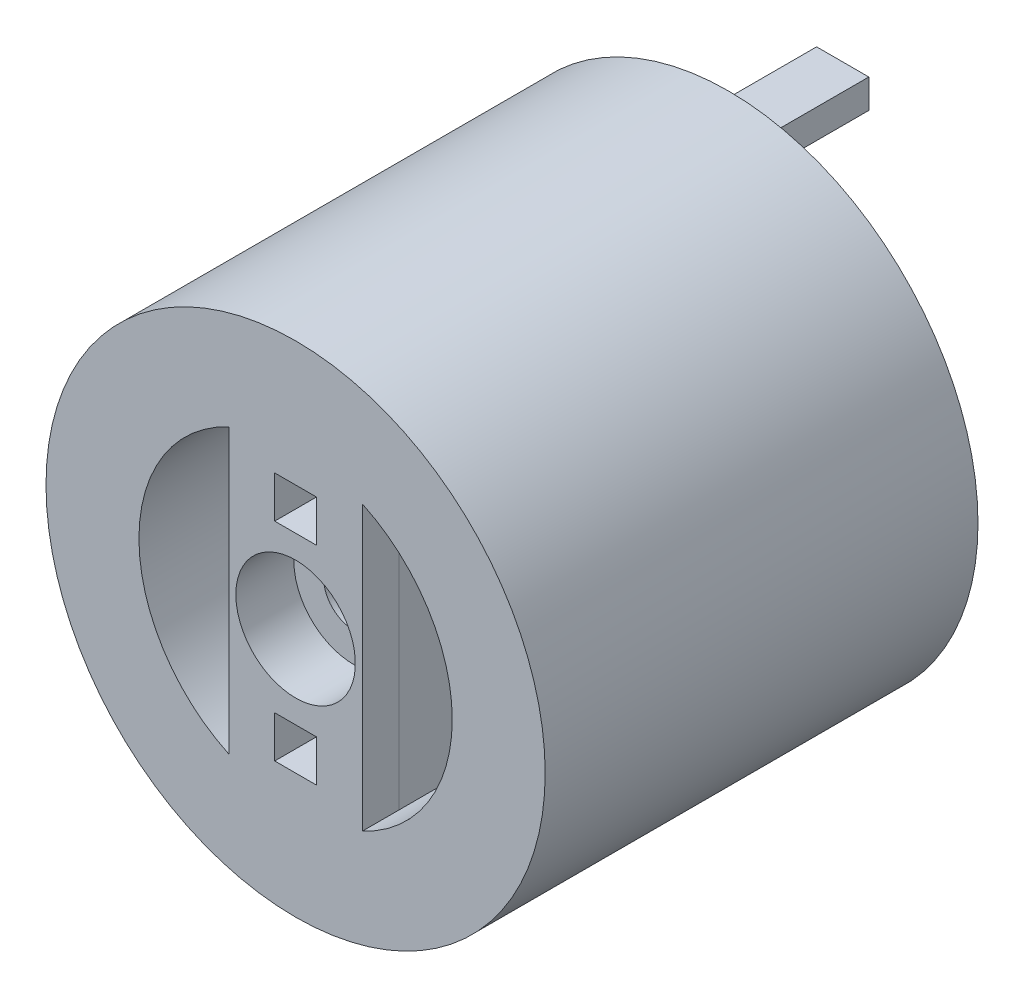
SolidWorks part; units mm, degrees
ref_plane "Front Plane" through (0, 0, 0) normal (0, 0, 1) x (1, 0, 0)
ref_plane "Top Plane" through (0, 0, 0) normal (0, 1, 0) x (1, 0, 0)
ref_plane "Right Plane" through (0, 0, 0) normal (1, 0, 0) x (0, 0, -1)
sketch "Sketch1" plane through (0, 0, 0) normal (0, 0, 1) x (1, 0, 0)
  line L0 (14.5003, 0) -> (13.5003, 0)
  line L1 (0, 16.2503) -> (0, 13.5003)
  line L3 (0, -13.5003) -> (0, -21.51)
  line L4 (13.5003, 0) -> (-13.5003, 0)
  line L8 (19.5347, 4.9654) -> (14.5348, 4.9999)
  line L9 (19.5347, 4.9654) -> (19.4657, -5.0344)
  line L10 (19.4657, -5.0344) -> (14.4659, -4.9999)
  line L11 (14.5348, 4.9999) -> (14.4659, -4.9999)
  line L24 (-2.25, 18.7503) -> (-2.25, 16.2503)
  line L25 (-2.25, 18.7503) -> (2.25, 18.7503)
  line L26 (2.25, 18.7503) -> (2.25, 16.2503)
  line L27 (-2.25, 16.2503) -> (2.25, 16.2503)
  circle A0 centre (0, 0) radius 13.5003
  circle A1 centre (0, 0) radius 21.51
  point P0 (0, 16.2503)
  point P1 (14.5003, 0)
  dimension "D3" = 4.5
  dimension "D5" = 4.9
  dimension "D1" = 1
  dimension "D2" = 2.75
  dimension "D4" = 2.5
  dimension "D6" = 5
  dimension "D7" = 10
extrude "Boss-Extrude1" add sketch "Sketch1" along normal blind 37.3 contours A1 L11 L8 L9 L10 L27 L24 L25 L26 A0 | L24 L27 L26 L25 | L8 L11 L10 L9 | L3 A1 L9 L10 L11 L0 A0 region at (-14.7797, 14.7797, 0) region at (0, 17.5003, 0) region at (17.0003, -0.0172, 0)
extrude "Boss-Extrude2" add sketch "Sketch1<4>" against normal blind 9.85 contours L25 L26 L27 L24
sketch "Sketch1<4>" plane through (0, 0, 0) normal (0, 0, 1) x (1, 0, 0) same geometry as "Sketch1"
sketch "Sketch3" plane through (0, 0, 0) normal (0, 1, 0) x (1, 0, 0)
  line L0 (0, -26.5014) -> (0, 0)
pattern_circular "CirPattern2" count 2 over 360 about axis through (0, 0, 26.5014) along (0, 0, -1) of "Boss-Extrude2" reverse direction yes
sketch "Sketch4" plane through (0, 0, 37.3) normal (0, 0, 1) x (1, 0, 0)
  line L1 (5.75, -19.1684) -> (-5.75, -19.1684)
  line L2 (5.75, -19.1684) -> (5.75, 19.1684)
  line L3 (5.75, 19.1684) -> (-5.75, 19.1684)
  line L4 (-5.75, -19.1684) -> (-5.75, 19.1684)
  line L5 (5.75, -19.1684) -> (-5.75, 19.1684) construction
  line L6 (5.75, 19.1684) -> (-5.75, -19.1684) construction
  line L7 (-5.75, 5.75) -> (5.75, 5.75)
  line L8 (-5.75, 5.75) -> (-5.75, -5.75)
  line L9 (-5.75, -5.75) -> (5.75, -5.75)
  line L10 (5.75, 5.75) -> (5.75, -5.75)
  line L11 (-5.75, 5.75) -> (5.75, -5.75) construction
  line L12 (-5.75, -5.75) -> (5.75, 5.75) construction
  point P0 (0, 0)
  point P5 (0, 0)
  point P11 (4.1064, -4.1064)
  dimension "D1" = 11.5
extrude "Boss-Extrude3" add sketch "Sketch4" against normal blind 3.175 contours L4 L3 L2 L1
sketch "Sketch8" plane through (0, 0, 34.125) normal (0, 0, 1) x (1, 0, 0)
  line L0 (0, -2.5875) -> (0, -16.4823)
  line L5 (5.7476, 16.4823) -> (-5.7476, 16.4823)
  line L6 (5.7476, 16.4823) -> (5.7476, -16.4823)
  line L11 (5.7476, -16.4823) -> (-5.7476, -16.4823)
  line L12 (-5.7476, 16.4823) -> (-5.7476, -16.4823)
  line L13 (5.7476, 16.4823) -> (-5.7476, -16.4823) construction
  line L14 (5.7476, -16.4823) -> (-5.7476, 16.4823) construction
  circle A1 centre (0, 0) radius 2.5875
  point P0 (0, 0)
  dimension "D2" = 11.4952
extrude "Boss-Extrude4" add sketch "Sketch8" against normal blind 5 contours L5 L12 L11 L6 | A1
extrude "Cut-Extrude1" cut sketch "Sketch1<3>" along normal blind 23 contours L8 L11 L10 L9 region at (17.0003, -0.0172, 0)
sketch "Sketch1<3>" plane through (0, 0, 0) normal (0, 0, 1) x (1, 0, 0) same geometry as "Sketch1"
pattern_circular "CirPattern1" count 2 every 53 about axis through (0, 0, 26.5014) along (0, 0, -1) of "Cut-Extrude1" reverse direction yes other way count 2
mirror "Mirror2" about plane through (0, 0, 0) normal (1, 0, 0) of "CirPattern1"
sketch "Sketch7" plane through (0, 0, 37.3) normal (0, 0, 1) x (1, 0, 0)
  circle A0 centre (0, 0) radius 5.15
extrude "Cut-Extrude2" cut sketch "Sketch7" against normal blind 5 and the other way through all
sketch "Sketch11" plane through (0, 0, 37.3) normal (0, 0, -1) x (-1, 0, 0)
  line L0 (0, 7.15) -> (0, 5.15)
  line L1 (-1.8, 10.75) -> (1.8, 10.75)
  line L2 (-1.8, 10.75) -> (-1.8, 7.15)
  line L3 (-1.8, 7.15) -> (1.8, 7.15)
  line L4 (1.8, 10.75) -> (1.8, 7.15)
  line L5 (-1.8, 10.75) -> (1.8, 7.15) construction
  line L6 (-1.8, 7.15) -> (1.8, 10.75) construction
  circle A0 centre (0, 0) radius 5.15 construction
  point P0 (0, 8.95)
  dimension "D1" = 3.6
  dimension "D2" = 2
extrude "Cut-Extrude21" cut sketch "Sketch11" along normal blind 29 contours L1 L4 L3 L2 region at (0, 8.95, 37.3)
mirror "Mirror1" about plane through (0, 0, 0) normal (0, 1, 0) of "Cut-Extrude21"
